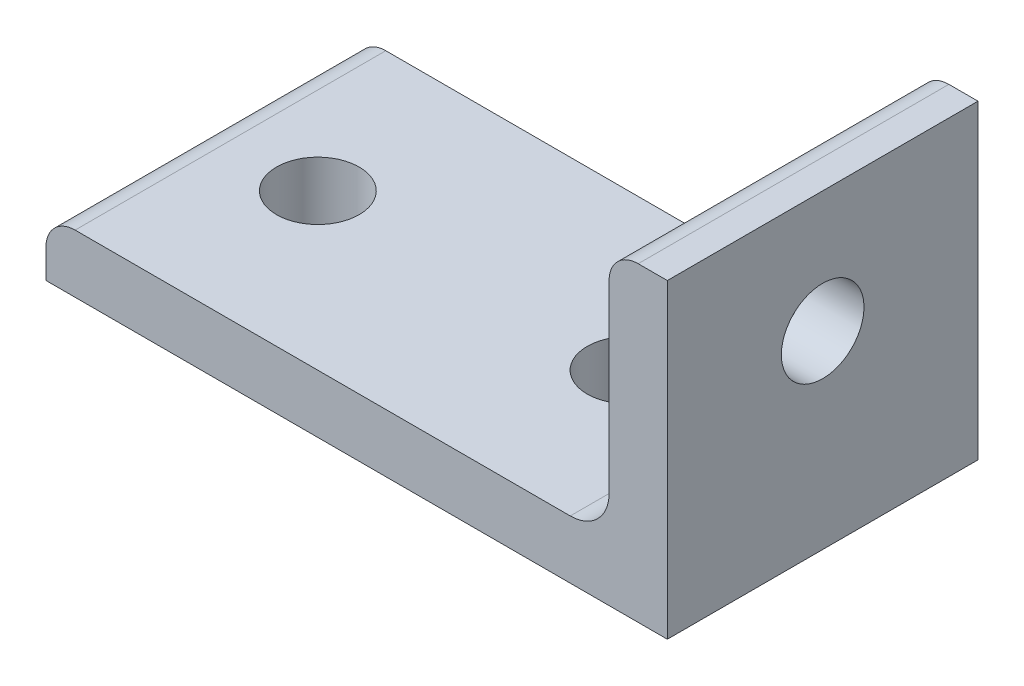
SolidWorks part; units mm, degrees
ref_plane "Front Plane" through (0, 0, 0) normal (0, 0, 1) x (1, 0, 0)
ref_plane "Top Plane" through (0, 0, 0) normal (0, 1, 0) x (1, 0, 0)
ref_plane "Right Plane" through (0, 0, 0) normal (1, 0, 0) x (0, 0, -1)
sketch "Sketch0" plane through (0, 0, 0) normal (0, 0, 1) x (1, 0, 0)
  line L0 (-25.4, -12.7) -> (25.4, -12.7)
  line L1 (25.4, -12.7) -> (25.4, 12.7)
  line L2 (25.4, 0) -> (0, 0) construction
  line L3 (0, 0) -> (0, -12.7) construction
  line L4 (20.6375, -4.7625) -> (20.6375, 12.7) construction
  line L5 (17.4625, -7.9375) -> (-25.4, -7.9375) construction
  arc A0 (20.6375, -4.7625) -> (17.4625, -7.9375) centre (17.4625, -4.7625) cw
  point P3 (19.7076, -7.0076)
  dimension "Inside Corner Radius" = 3.175
  dimension "Outside Height" = 25.4
  dimension "Inside Height" = 20.6375
  dimension "Inside Width" = 46.0375
  dimension "Wall Thickness" = 4.7625
  dimension "D1" = 4.7625
  dimension "Outside Width" = 50.8
sketch "Sketch1" plane through (0, 0, 0) normal (1, 0, 0) x (0, 0, -1)
  line L0 (12.7, 0) -> (-12.7, 0)
  point P4 (0, 0)
  dimension "Length" = 25.4
sketch "Sketch2" plane through (0, 0, 0) normal (0, 0, 1) x (1, 0, 0)
  line L0 (-25.4, -12.7) -> (25.4, -12.7)
  line L1 (25.4, -12.7) -> (25.4, 12.7)
  line L2 (25.4, 12.7) -> (20.6375, 12.7) construction
  line L3 (20.6375, 10.3188) -> (20.6375, -4.7625)
  line L4 (17.4625, -7.9375) -> (-23.0188, -7.9375)
  line L5 (-25.4, -12.7) -> (-25.4, -7.9375) construction
  line L6 (23.0187, 12.7) -> (25.4, 12.7)
  line L7 (-25.4, -10.3188) -> (-25.4, -12.7)
  line L8 (25.4, 0) -> (0, 0) construction
  line L9 (0, 0) -> (0, -12.7) construction
  arc A0 (20.6375, 10.3188) -> (23.0187, 12.7) centre (23.0187, 10.3188) cw
  arc A1 (-25.4, -10.3188) -> (-23.0188, -7.9375) centre (-23.0188, -10.3188) cw
  arc A2 (20.6375, -4.7625) -> (17.4625, -7.9375) centre (17.4625, -4.7625) cw
  dimension "Inside Radius" = 3.175
  dimension "Height" = 25.4
  dimension "Width" = 50.8
  dimension "Thickness" = 4.7625
extrude "Boss-Extrude1" add sketch "Sketch2" along normal mid plane 25.4
sketch "Break Locations" plane through (0, 0, 0) normal (1, 0, 0) x (0, 0, -1)
  line L0 (13.208, 0) -> (-13.208, 0)
  line L1 (-12.7, -12.7) -> (-12.7, 12.7) construction
  line L2 (12.7, -12.7) -> (12.7, 12.7) construction
  point P0 (8.89, 0)
  point P1 (-8.89, 0)
  point P10 (0, 0)
  point P11 (-13.208, 0)
  point P13 (13.208, 0)
  dimension "D1" = 21.59
  dimension "D2" = 21.59
  dimension "D3" = 25.908
hole_wizard "1/4 Clearance Hole1" positions "Sketch6" profile "Sketch7" hole size "1/4" standard "ANSI Inch" end condition through all
sketch "Sketch6" plane through (20.6375, 0, 0) normal (-1, 0, 0) x (0, 0, 1)
  line L0 (-12.7, 2.7781) -> (12.7, 2.7781) construction
  line L1 (-12.7, 10.3188) -> (-12.7, -4.7625) construction
  line L2 (12.7, 10.3188) -> (12.7, -4.7625) construction
  point P9 (0, 2.7781)
sketch "Sketch7" plane through (20.6375, 2.7781, 0) normal (0, 1, 0) x (0, 0, 1)
  line L0 (0, 0) -> (0, 4.7625)
  line L1 (0, 4.7625) -> (3.3782, 4.7625)
  line L2 (3.3782, 4.7625) -> (3.3782, 0)
  line L5 (3.3782, 0) -> (0, 0)
  line L11 (0, -6.35) -> (0, 107.95) construction
  dimension "Thru Hole Dia." = 6.7564
  dimension "Thru Hole Depth" = 4.7625
hole_wizard "1/4 Clearance Hole2" positions "Sketch8" profile "Sketch9" hole size "1/4" standard "ANSI Inch" end condition through all
sketch "Sketch8" plane through (0, -7.9375, 0) normal (0, 1, 0) x (1, 0, 0)
  line L0 (-23.0188, 0) -> (17.4625, 0) construction
  line L1 (-23.0188, -12.7) -> (-23.0188, 12.7) construction
  line L2 (17.4625, -12.7) -> (17.4625, 12.7) construction
  line L3 (-25.4, -12.7) -> (-25.4, 12.7) construction
  point P9 (-15.875, 0)
  point P11 (9.525, 0)
  dimension "D1" = 9.525
  dimension "D2" = 25.4
sketch "Sketch9" plane through (9.525, -7.9375, 0) normal (1, 0, 0) x (0, 0, 1)
  line L0 (0, 0) -> (0, 4.7625)
  line L1 (0, 4.7625) -> (3.3782, 4.7625)
  line L2 (3.3782, 4.7625) -> (3.3782, 0)
  line L5 (3.3782, 0) -> (0, 0)
  line L11 (0, -6.35) -> (0, 107.95) construction
  dimension "Thru Hole Dia." = 6.7564
  dimension "Thru Hole Depth" = 4.7625
equation "\"D1@Break Locations\" = .85 * \"Height@Sketch2\""
equation "\"D2@Break Locations\"=\"D1@Break Locations\""
equation "\"Thickness@Sketch2\" = \"Wall Thickness@Sketch0\""
equation "\"Height@Sketch2\" = \"Outside Height@Sketch0\""
equation "\"Width@Sketch2\" = \"Outside Width@Sketch0\""
equation "\"Inside Radius@Sketch2\" = \"Inside Corner Radius@Sketch0\""
equation "\"Length@Boss-Extrude1\"= \"Length@Sketch1\""
equation "\"D3@Break Locations\"=\"D2@Break Locations\"*1.2"
equation "\"D1@Sketch0\"=\"Wall Thickness@Sketch0\""
equation "\"length\"= 1in"
equation "\"Length@Sketch1\"=\"length\""
